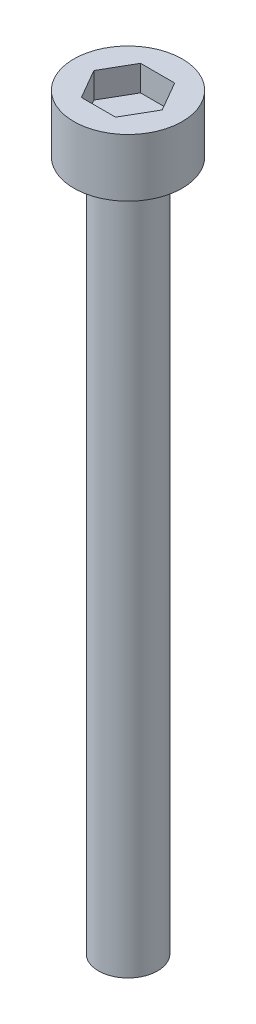
SolidWorks part; units mm, degrees
ref_plane "前视基准面" through (0, 0, 0) normal (0, 0, 1) x (1, 0, 0)
ref_plane "上视基准面" through (0, 0, 0) normal (0, 1, 0) x (1, 0, 0)
ref_plane "右视基准面" through (0, 0, 0) normal (1, 0, 0) x (0, 0, -1)
sketch "草图1" plane through (0, 0, 0) normal (0, 1, 0) x (1, 0, 0)
  line L1 (0.866, 1.5) -> (-0.866, 1.5)
  line L2 (-0.866, 1.5) -> (-1.7321, 0)
  line L3 (-1.7321, 0) -> (-0.866, -1.5)
  line L4 (-0.866, -1.5) -> (0.866, -1.5)
  line L5 (0.866, -1.5) -> (1.7321, 0)
  line L6 (1.7321, 0) -> (0.866, 1.5)
  circle A0 centre (0, 0) radius 2.75
  circle A1 centre (0, 0) radius 1.5 construction
  dimension "D1" = 5.5
  dimension "D2" = 3
extrude "凸台-拉伸1" add sketch "草图1" along normal blind 2.93
extrude "凸台-拉伸2" add sketch "草图1<2>" along normal offset from surface (1.63 mm away) 1.3 contours L2 L3 L4 L5 L6 L1 up to face at (0, 2.93, 2.75)
sketch "草图1<2>" plane through (0, 0, 0) normal (0, 1, 0) x (1, 0, 0) same geometry as "草图1"
sketch "草图2" plane through (0, 0, 0) normal (0, -1, 0) x (1, 0, 0)
  circle A0 centre (0, 0) radius 1.5
  dimension "D1" = 3
extrude "凸台-拉伸3" add sketch "草图2" along normal blind 35
cosmetic thread "装饰螺纹线1" parameters "D2"=2.5
